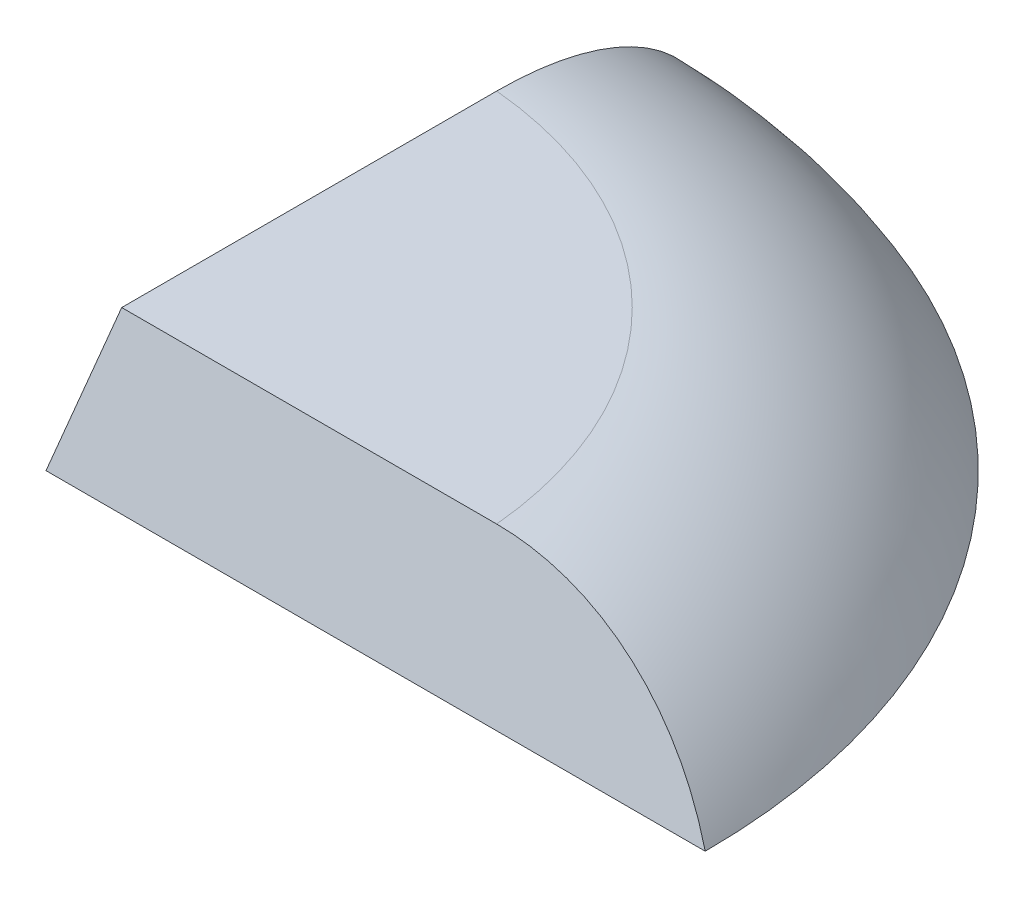
SolidWorks part; units mm, degrees
material "ABS"
ref_plane "Front Plane" through (0, 0, 0) normal (0, 0, 1) x (1, 0, 0)
ref_plane "Top Plane" through (0, 0, 0) normal (0, 1, 0) x (1, 0, 0)
ref_plane "Right Plane" through (0, 0, 0) normal (1, 0, 0) x (0, 0, -1)
sketch "Sketch1" plane through (0, 0, 0) normal (0, 1, 0) x (1, 0, 0)
  line L1 (-17.5, 17.5) -> (17.5, 17.5)
  line L2 (-17.5, 17.5) -> (-17.5, -17.5)
  line L3 (-17.5, -17.5) -> (17.5, -17.5)
  line L4 (17.5, 17.5) -> (17.5, -17.5)
  line L5 (-17.5, 17.5) -> (17.5, -17.5) construction
  line L6 (-17.5, -17.5) -> (17.5, 17.5) construction
  point P0 (0, 0)
  dimension "D1" = 35
sketch "Sketch2" plane through (0, 0, 0) normal (0, 1, 0) x (1, 0, 0)
  line L0 (-17.0442, -3.0442) -> (-17.0442, -17.0442)
  line L1 (-17.0442, -17.0442) -> (-3.0442, -17.0442)
  line L2 (-17.5, -17.5) -> (17.5, 17.5) construction
  arc A0 (-17.0442, -3.0442) -> (-3.0442, -17.0442) centre (-17.0442, -17.0442) cw
  point P3 (0, 0)
  point P6 (-17.0442, -17.0442)
  dimension "D1" = 14
extrude "Boss-Extrude1" add sketch "Sketch2" along normal blind 3 draft 15
fillet "Fillet1" radius 6 1 edges at (-7.7131, 3, 7.7131)
